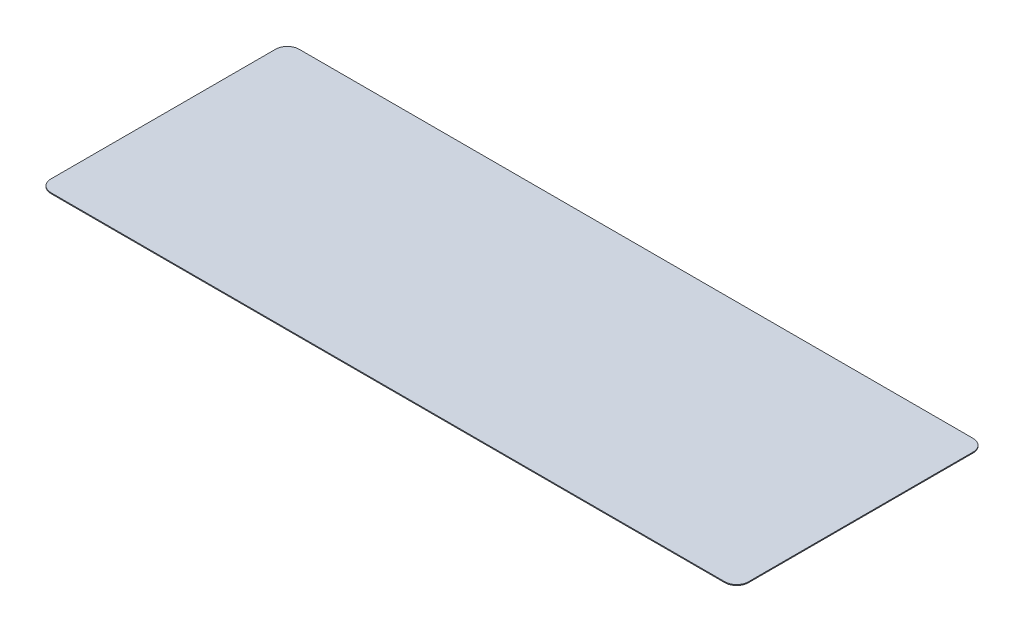
SolidWorks part; units mm, degrees
material "AISI 1020 Steel, Cold Rolled"
ref_plane "Front Plane" through (0, 0, 0) normal (0, 0, 1) x (1, 0, 0)
ref_plane "Top Plane" through (0, 0, 0) normal (0, 1, 0) x (1, 0, 0)
ref_plane "Right Plane" through (0, 0, 0) normal (1, 0, 0) x (0, 0, -1)
sketch "Sketch1" plane through (0, 0, 0) normal (0, 1, 0) x (1, 0, 0)
  line L1 (-295, 105) -> (295, 105)
  line L2 (-295, 105) -> (-295, -105)
  line L3 (-295, -105) -> (295, -105)
  line L4 (295, 105) -> (295, -105)
  line L5 (-295, 105) -> (295, -105) construction
  line L6 (-295, -105) -> (295, 105) construction
  point P0 (0, 0)
  dimension "D1" = 590
  dimension "D2" = 210
extrude "Boss-Extrude1" add sketch "Sketch1" along normal blind 0.76
fillet "Fillet1" radius 10 4 edges at (-295, 0.38, 105) (295, 0.38, 105) (295, 0.38, -105) (-295, 0.38, -105)
